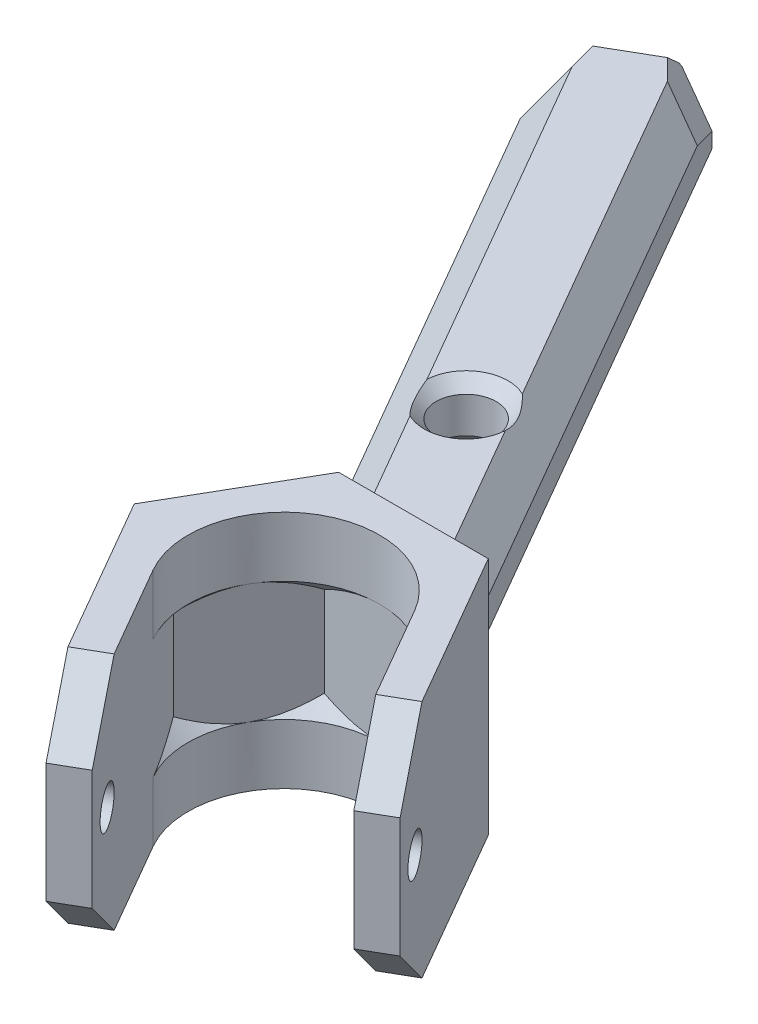
SolidWorks part; units mm, degrees
ref_plane "Front Plane" through (0, 0, 0) normal (0, 0, 1) x (1, 0, 0)
ref_plane "Top Plane" through (0, 0, 0) normal (0, 1, 0) x (1, 0, 0)
ref_plane "Right Plane" through (0, 0, 0) normal (1, 0, 0) x (0, 0, -1)
sketch "Sketch1" plane through (0, 0, 0) normal (0, 1, 0) x (1, 0, 0)
  line L0 (-12.5, 0) -> (-24.375, 20.5681)
  line L5 (4.6188, 8) -> (-4.6188, 8)
  line L6 (-4.6188, 8) -> (-9.2376, 0)
  line L7 (-9.2376, 0) -> (-4.6188, -8)
  line L8 (-4.6188, -8) -> (4.6188, -8)
  line L9 (4.6188, -8) -> (9.2376, 0)
  line L10 (9.2376, 0) -> (4.6188, 8)
  line L11 (-12.5, 0) -> (-6.25, -10.8253)
  line L12 (-6.25, -10.8253) -> (6.25, -10.8253)
  line L13 (6.25, -10.8253) -> (12.5, 0)
  line L14 (12.5, 0) -> (6.25, 10.8253)
  line L15 (6.25, 10.8253) -> (-6.25, 10.8253)
  line L16 (-6.25, 10.8253) -> (-12.5, 0)
  line L17 (-24.375, 20.5681) -> (-5.625, 31.3934)
  line L18 (-5.625, 31.3934) -> (6.25, 10.8253)
  circle A0 centre (0, 0) radius 8
  circle A1 centre (0, 0) radius 10.8253 construction
  circle A2 centre (0, 0) radius 12.5
  dimension "D1" = 16
  dimension "D2" = 25
  dimension "D3" = 30
extrude "Boss-Extrude1" add sketch "Sketch1" along normal mid plane 20 contours L13 L14 L15 L16 L11 L12 L7 L6 L5 L10 | L13 L9 L8 L12 | A0 L9 L10 | A0 L10 L5 | A0 L5 L6 | A0 L6 L7 | A0 L7 L8 | A0 L8 L9 region at (-9.0886, 0, -5.2473) region at (4.1343, 0, -7.1607) region at (-4.1343, 0, -7.1607) region at (8.2685, 0, 0) region at (-8.2685, 0, 0) region at (-4.1343, 0, 7.1607) region at (4.1343, 0, 7.1607)
extrude "Cut-Extrude3" cut sketch "Sketch1<3>" against normal mid plane 10 contours A0 L9 L10 | A0 L10 L5 | A0 L5 L6 | A0 L6 L7 | A0 L7 L8 | A0 L8 L9 | A0 region at (4.1343, 0, -7.1607) region at (-4.1343, 0, -7.1607) region at (0, 0, 0) region at (8.2685, 0, 0) region at (-8.2685, 0, 0) region at (-4.1343, 0, 7.1607) region at (4.1343, 0, 7.1607)
sketch "Sketch1<3>" plane through (0, 0, 0) normal (0, 1, 0) x (1, 0, 0) same geometry as "Sketch1"
sketch "Sketch2" plane through (0, 0, 0) normal (1, 0, 0) x (0, 0, -1)
  line L0 (9.24, 10) -> (8, 10)
  line L2 (8, 10) -> (8, 5)
  line L3 (8, 5) -> (9.24, 3.76)
  line L5 (9.24, 3.76) -> (9.24, 10)
  line L6 (8, 5) -> (9.24, 5) construction
  line L7 (0, 0) -> (0, 4.3695) construction
  line L8 (8, 10) -> (-8, 10) construction
  line L9 (8, 10) -> (-8, 10) construction
  point P3 (0, 0)
  point P8 (0, 0)
  point P9 (0, 0)
  point P12 (0, 4.3695)
  point P13 (0, 0)
  point P16 (0, 0)
  point P17 (0, 0)
  point P18 (0, 0)
  point P19 (0, 0)
  point P20 (6.9696, 3.76)
  point P21 (0, 0)
  point P22 (0, 0)
  point P26 (0, 0)
  point P27 (0, 0)
  dimension "D1" = 45
  dimension "D2" = 5
  dimension "D3" = 1.24
revolve "Revolve1" add sketch "Sketch2" angle 360 about L7
mirror "Mirror1" about plane through (0, 0, 0) normal (0, 1, 0) of "Revolve1"
sketch "Sketch3" plane through (0, 0, 0) normal (0, 1, 0) x (1, 0, 0)
  line L0 (-6.9282, -4) -> (6.9282, 4)
  line L1 (-4.6188, -8) -> (-6.9282, -4) construction
  line L4 (6.9282, 4) -> (9.2376, 0) construction
  line L5 (6.9282, 4) -> (13.3704, -7.1583)
  line L6 (13.3704, -7.1583) -> (-0.486, -15.1583)
  line L7 (-0.486, -15.1583) -> (-6.9282, -4)
  circle A0 centre (0, 0) radius 8 construction
  point P4 (0, 0)
  point P5 (-6.9282, -4)
  point P6 (7.056, 3.7699)
extrude "Cut-Extrude6" cut sketch "Sketch3" against normal through all both and the other way through all
ref_plane "Plane1" through (0, -10, 0) normal (0, -1, 0) x (-1, 0, 0)
sketch "Sketch4" plane through (0, -10, 0) normal (0, -1, 0) x (-1, 0, 0)
  line L0 (0, 10.8253) -> (35.3125, 71.9884)
  line L1 (-6.25, 10.8253) -> (6.25, 10.8253) construction
  line L2 (35.3125, 71.9884) -> (44.6875, 66.5757)
  line L3 (44.6875, 66.5757) -> (9.375, 5.4127)
  line L4 (6.25, 10.8253) -> (12.5, 0) construction
  line L5 (0, 10.8253) -> (6.25, 10.8253)
  line L6 (6.25, 10.8253) -> (9.375, 5.4127)
  line L7 (12.5, 0) -> (6.25, -10.8253) construction
  line L8 (10.9375, 8.119) -> (12.5, 0)
  line L9 (-6.25, 10.8253) -> (1.5625, 13.5316)
  line L10 (1.5625, 13.5316) -> (10.9375, 8.119) construction
  line L11 (-6.25, 10.8253) -> (0, 10.8253)
  line L12 (9.375, 5.4127) -> (12.5, 0)
  dimension "D1" = 80
extrude "Boss-Extrude2" add sketch "Sketch4" against normal blind 5 contours L9 L11 L0 | L10 L0 L5 | L0 L10 L3 L2 | L10 L6 L3 | L3 L12 L8 region at (1.5625, -10, -11.7274) region at (-2.6042, -10, -11.7274) region at (-23.125, -10, -40.0537) region at (-8.8542, -10, -8.119) region at (-10.9375, -10, -4.5105)
chamfer "Chamfer1" distance 5 angle 45 2 edges at (0, -5, -10.8253) (-9.375, -5, -5.4127)
chamfer "Chamfer2" distance 2.5 angle 45 2 edges at (-19.0996, -5, -43.9068) (-28.4746, -5, -38.4942)
chamfer "Chamfer3" distance 2.5 angle 45 2 edges at (-35.3125, -8.75, -71.9884) (-44.6875, -8.75, -66.5757)
chamfer "Chamfer4" distance 1 angle 45 3 edges at (-42.98, -6.25, -66.1182) (-35.77, -6.25, -70.2808) (-40, -5, -69.282) first distance on face at (-42.98, -8.125, -66.1182) first distance on face at (-35.77, -8.125, -70.2808) first distance on face at (-40, -7.5, -69.282)
sketch "Sketch5" plane through (0, -10, 0) normal (0, -1, 0) x (1, 0, 0)
  line L0 (-41.9641, -64.684) -> (-35.0359, -68.684)
  line L1 (-35.0359, -68.684) -> (-22.3359, -46.6869)
  line L2 (-22.3359, -46.6869) -> (-29.2641, -42.6869)
  line L3 (-29.2641, -42.6869) -> (-41.9641, -64.684)
  line L4 (-37.4776, -70.7384) -> (-42.5224, -67.8257) construction
  line L5 (-40, -69.282) -> (-38.5, -66.684) construction
  line L6 (-25.8, -44.6869) -> (-20.8, -36.0267) construction
  circle A0 centre (-20.8, -36.0267) radius 2.5
  dimension "D5" = 5
  dimension "D1" = 8
  dimension "D2" = 3
  dimension "D3" = 25.4
  dimension "D4" = 10
extrude "Cut-Extrude7" cut sketch "Sketch5" against normal blind 0.6 contours L2 L3 L0 L1 region at (-32.15, -10, -55.6854)
extrude "Cut-Extrude8" cut sketch "Sketch5<3>" against normal through all contours A0 region at (-20.8, -10, -36.0267)
sketch "Sketch5<3>" plane through (0, -10, 0) normal (0, -1, 0) x (1, 0, 0) same geometry as "Sketch5"
chamfer "Chamfer5" distance 1 angle 45 2 edges at (-20.8, -5, -38.5267) (-20.8, -10, -38.5267)
sketch "Sketch6" plane through (0, -10, 0) normal (0, -1, 0) x (-1, 0, 0)
  line L0 (-10.8688, -2.8253) -> (-13.8688, -8.0215)
  line L1 (-13.8688, -8.0215) -> (-16.3156, -6.6088)
  line L2 (-16.3156, -6.6088) -> (-12.5, 0)
  line L3 (-10.8688, -2.8253) -> (-6.9282, 4) construction
  line L4 (-12.5, 0) -> (-10.8688, -2.8253)
  dimension "D1" = 6
extrude "Boss-Extrude3" add sketch "Sketch6" against normal up to surface (20 mm away) up to face at (-0.2632, 10, -0.4559)
chamfer "Chamfer6" distance 5 angle 45 2 edges at (15.0922, -10, 7.3151) (15.0922, 10, 7.3151)
sketch "Sketch7" plane through (9.375, 0, -5.4127) normal (0.866, 0, -0.5) x (-0.5, 0, -0.866)
  line L2 (-13.8812, 5) -> (-13.8812, -5) construction
  circle A0 centre (-10.4812, 0) radius 1.6
  circle A1 centre (-10.4812, 0) radius 2.8 construction
  point P7 (-13.8812, 0)
  dimension "D1" = 3.2
  dimension "D3" = 5.6
  dimension "D2" = 1.6
extrude "Cut-Extrude9" cut sketch "Sketch7" against normal up to next
ref_plane "Plane2" through (0, 0, 0) normal (0.866, 0, -0.5) x (-0.5, 0, -0.866)
mirror "Mirror2" about plane through (0, 0, 0) normal (0.866, 0, -0.5) of "Boss-Extrude3", "Chamfer6", "Cut-Extrude9"
